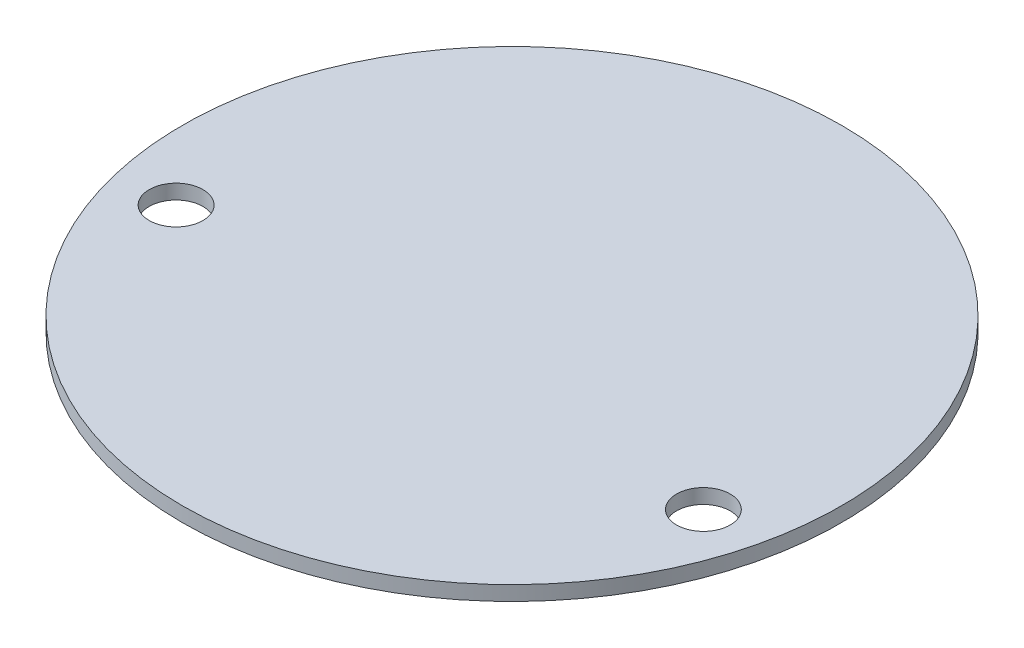
SolidWorks part; units mm, degrees
material "ABS"
ref_plane "Front Plane" through (0, 0, 0) normal (0, 0, 1) x (1, 0, 0)
ref_plane "Top Plane" through (0, 0, 0) normal (0, 1, 0) x (1, 0, 0)
ref_plane "Right Plane" through (0, 0, 0) normal (1, 0, 0) x (0, 0, -1)
sketch "Sketch1" plane through (0, 0, 0) normal (0, 1, 0) x (1, 0, 0)
  line L0 (-27, -7.4) -> (27, -7.4) construction
  circle A0 centre (0, 0) radius 33.75
  circle A1 centre (-27, -7.4) radius 2.75
  circle A2 centre (27, -7.4) radius 2.75
  point P7 (0, -7.4)
  dimension "D2" = 5.5
  dimension "D3" = 67.5
  dimension "D1" = 54
  dimension "D4" = 7.4
extrude "Boss-Extrude1" add sketch "Sketch1" along normal blind 1.5
